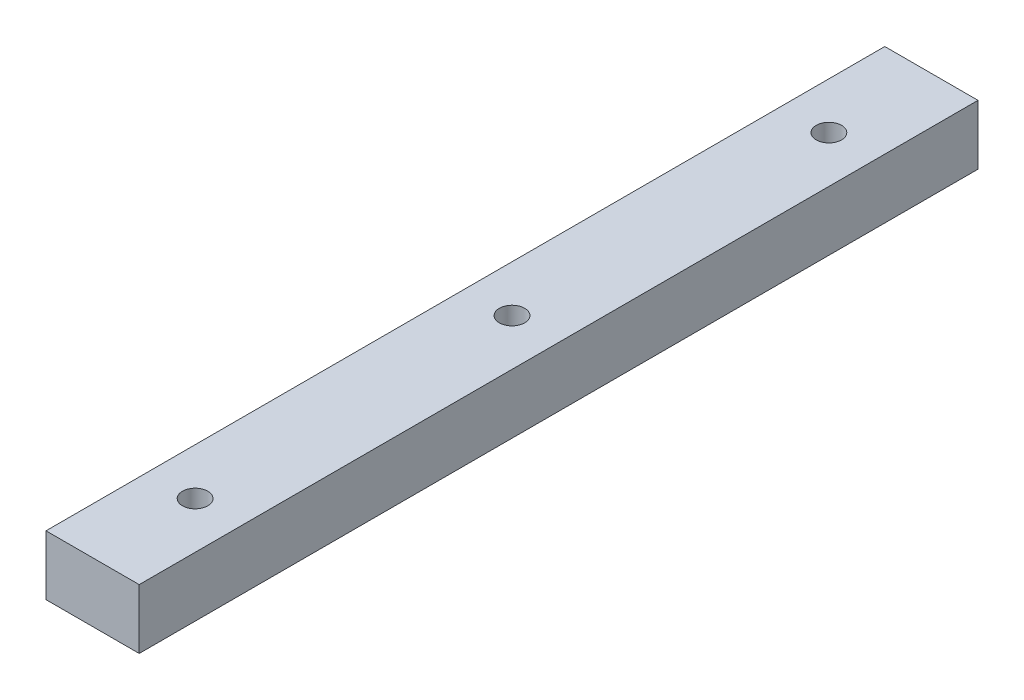
SolidWorks part; units mm, degrees
material "Plain Carbon Steel"
ref_plane "Front Plane" through (0, 0, 0) normal (0, 0, 1) x (1, 0, 0)
ref_plane "Top Plane" through (0, 0, 0) normal (0, 1, 0) x (1, 0, 0)
ref_plane "Right Plane" through (0, 0, 0) normal (1, 0, 0) x (0, 0, -1)
sketch "Sketch1" plane through (0, 0, 0) normal (0, 1, 0) x (1, 0, 0)
  line L1 (-12.5, -112.5) -> (12.5, -112.5)
  line L2 (-12.5, -112.5) -> (-12.5, 112.5)
  line L3 (-12.5, 112.5) -> (12.5, 112.5)
  line L4 (12.5, -112.5) -> (12.5, 112.5)
  line L5 (-12.5, -112.5) -> (12.5, 112.5) construction
  line L6 (-12.5, 112.5) -> (12.5, -112.5) construction
  point P0 (0, 0)
  dimension "D1" = 225
  dimension "D2" = 25
extrude "Boss-Extrude1" add sketch "Sketch1" against normal blind 16
sketch "Sketch2" plane through (0, -16, 0) normal (0, -1, 0) x (1, 0, 0)
  circle A0 centre (0, -100) radius 7.5 construction
  circle A1 centre (0, 100) radius 7.5 construction
  circle A2 centre (0, -100) radius 7.5 construction
  circle A3 centre (0, 100) radius 7.5 construction
  circle A4 centre (0, 100) radius 8.5
  circle A5 centre (0, -100) radius 8.5
  dimension "D1" = 17
extrude "Cut-Extrude1" cut sketch "Sketch2" against normal blind 5
hole_wizard "M8 Tapped Hole1" positions "Sketch7" profile "Sketch6" tap size "M8" standard "ISO" end condition through all
sketch "Sketch7" plane through (0, 0, 0) normal (0, 1, 0) x (1, 0, 0)
  point P0 (0, 85)
  point P2 (0, 0)
  point P4 (0, -85)
  point P7 (0, 0)
  dimension "D1" = 0
  dimension "D2" = 85
  dimension "D3" = 85
sketch "Sketch6" plane through (0, 0, -85) normal (1, 0, 0) x (0, 0, 1)
  line L0 (0, 0) -> (0, 16)
  line L1 (0, 16) -> (3.4, 16)
  line L2 (3.4, 16) -> (3.4, 0)
  line L5 (3.4, 0) -> (0, 0)
  line L11 (0, -6.35) -> (0, 107.95) construction
  dimension "Thru Tap Drill Dia." = 6.8
  dimension "Thru Tap Drill Depth" = 16
cosmetic thread "Hole Thread1"
cosmetic thread "Hole Thread2"
cosmetic thread "Hole Thread3"
